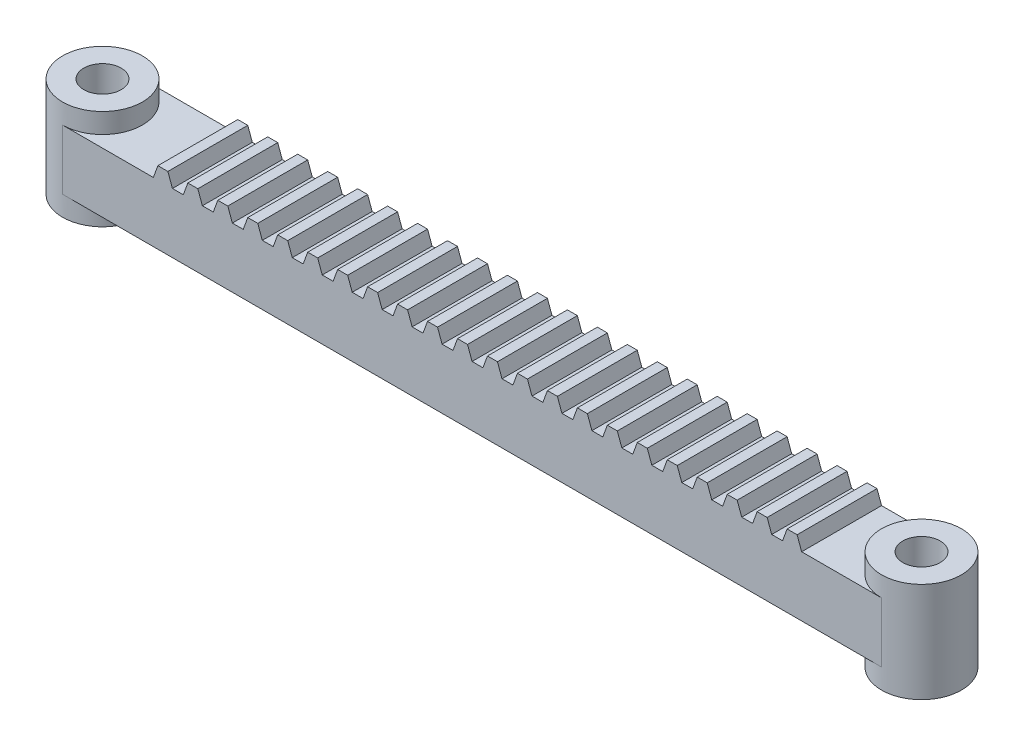
SolidWorks part; units mm, degrees
ref_plane "Front Plane" through (0, 0, 0) normal (0, 0, 1) x (1, 0, 0)
ref_plane "Top Plane" through (0, 0, 0) normal (0, 1, 0) x (1, 0, 0)
ref_plane "Right Plane" through (0, 0, 0) normal (1, 0, 0) x (0, 0, -1)
sketch "Sketch1" plane through (0, 0, 0) normal (0, 0, 1) x (1, 0, 0)
  line L0 (0, 12) -> (0, 0) construction
  line L1 (-82, 0) -> (82, 0)
  line L2 (82, 0) -> (82, 12)
  line L3 (82, 12) -> (66, 12)
  line L4 (-82, 0) -> (-82, 12)
  line L5 (-82, 12) -> (-63.8199, 12)
  line L7 (0, 12) -> (-0.9099, 14.5)
  line L8 (-0.9099, 14.5) -> (-2.9099, 14.5)
  line L9 (-2.9099, 14.5) -> (-3.8199, 12)
  line L10 (-3.8199, 12) -> (-6, 12)
  line L11 (-1.9099, 14.5019) -> (-1.9099, 13.6458) construction
  line L12 (6, 12) -> (5.0901, 14.5)
  line L13 (5.0901, 14.5) -> (3.0901, 14.5)
  line L14 (3.0901, 14.5) -> (2.1801, 12)
  line L15 (2.1801, 12) -> (0, 12)
  line L16 (-6.9099, 14.5) -> (-8.9099, 14.5)
  line L17 (4.0901, 14.5019) -> (4.0901, 13.6458) construction
  line L18 (12, 12) -> (11.0901, 14.5)
  line L19 (11.0901, 14.5) -> (9.0901, 14.5)
  line L20 (9.0901, 14.5) -> (8.1801, 12)
  line L21 (8.1801, 12) -> (6, 12)
  line L22 (-8.9099, 14.5) -> (-9.8199, 12)
  line L23 (10.0901, 14.5019) -> (10.0901, 13.6458) construction
  line L24 (18, 12) -> (17.0901, 14.5)
  line L25 (17.0901, 14.5) -> (15.0901, 14.5)
  line L26 (15.0901, 14.5) -> (14.1801, 12)
  line L27 (14.1801, 12) -> (12, 12)
  line L28 (-9.8199, 12) -> (-12, 12)
  line L29 (16.0901, 14.5019) -> (16.0901, 13.6458) construction
  line L30 (24, 12) -> (23.0901, 14.5)
  line L31 (23.0901, 14.5) -> (21.0901, 14.5)
  line L32 (21.0901, 14.5) -> (20.1801, 12)
  line L33 (20.1801, 12) -> (18, 12)
  line L34 (-7.9099, 14.5019) -> (-7.9099, 13.6458) construction
  line L35 (22.0901, 14.5019) -> (22.0901, 13.6458) construction
  line L36 (30, 12) -> (29.0901, 14.5)
  line L37 (29.0901, 14.5) -> (27.0901, 14.5)
  line L38 (27.0901, 14.5) -> (26.1801, 12)
  line L39 (26.1801, 12) -> (24, 12)
  line L40 (-6, 12) -> (-6.9099, 14.5)
  line L41 (28.0901, 14.5019) -> (28.0901, 13.6458) construction
  line L42 (36, 12) -> (35.0901, 14.5)
  line L43 (35.0901, 14.5) -> (33.0901, 14.5)
  line L44 (33.0901, 14.5) -> (32.1801, 12)
  line L45 (32.1801, 12) -> (30, 12)
  line L46 (-12.9099, 14.5) -> (-14.9099, 14.5)
  line L47 (34.0901, 14.5019) -> (34.0901, 13.6458) construction
  line L48 (42, 12) -> (41.0901, 14.5)
  line L49 (41.0901, 14.5) -> (39.0901, 14.5)
  line L50 (39.0901, 14.5) -> (38.1801, 12)
  line L51 (38.1801, 12) -> (36, 12)
  line L52 (-14.9099, 14.5) -> (-15.8199, 12)
  line L53 (40.0901, 14.5019) -> (40.0901, 13.6458) construction
  line L54 (48, 12) -> (47.0901, 14.5)
  line L55 (47.0901, 14.5) -> (45.0901, 14.5)
  line L56 (45.0901, 14.5) -> (44.1801, 12)
  line L57 (44.1801, 12) -> (42, 12)
  line L58 (-15.8199, 12) -> (-18, 12)
  line L59 (46.0901, 14.5019) -> (46.0901, 13.6458) construction
  line L60 (54, 12) -> (53.0901, 14.5)
  line L61 (53.0901, 14.5) -> (51.0901, 14.5)
  line L62 (51.0901, 14.5) -> (50.1801, 12)
  line L63 (50.1801, 12) -> (48, 12)
  line L64 (-13.9099, 14.5019) -> (-13.9099, 13.6458) construction
  line L65 (52.0901, 14.5019) -> (52.0901, 13.6458) construction
  line L66 (60, 12) -> (59.0901, 14.5)
  line L67 (59.0901, 14.5) -> (57.0901, 14.5)
  line L68 (57.0901, 14.5) -> (56.1801, 12)
  line L69 (56.1801, 12) -> (54, 12)
  line L70 (-12, 12) -> (-12.9099, 14.5)
  line L71 (58.0901, 14.5019) -> (58.0901, 13.6458) construction
  line L72 (66, 12) -> (65.0901, 14.5)
  line L73 (65.0901, 14.5) -> (63.0901, 14.5)
  line L74 (63.0901, 14.5) -> (62.1801, 12)
  line L75 (62.1801, 12) -> (60, 12)
  line L76 (-18.9099, 14.5) -> (-20.9099, 14.5)
  line L77 (64.0901, 14.5019) -> (64.0901, 13.6458) construction
  line L78 (-20.9099, 14.5) -> (-21.8199, 12)
  line L79 (-21.8199, 12) -> (-24, 12)
  line L80 (-19.9099, 14.5019) -> (-19.9099, 13.6458) construction
  line L81 (-18, 12) -> (-18.9099, 14.5)
  line L82 (-24.9099, 14.5) -> (-26.9099, 14.5)
  line L83 (-26.9099, 14.5) -> (-27.8199, 12)
  line L84 (-27.8199, 12) -> (-30, 12)
  line L85 (-25.9099, 14.5019) -> (-25.9099, 13.6458) construction
  line L86 (-24, 12) -> (-24.9099, 14.5)
  line L87 (-30.9099, 14.5) -> (-32.9099, 14.5)
  line L88 (-32.9099, 14.5) -> (-33.8199, 12)
  line L89 (-33.8199, 12) -> (-36, 12)
  line L90 (-31.9099, 14.5019) -> (-31.9099, 13.6458) construction
  line L91 (-30, 12) -> (-30.9099, 14.5)
  line L92 (-36.9099, 14.5) -> (-38.9099, 14.5)
  line L93 (-38.9099, 14.5) -> (-39.8199, 12)
  line L94 (-39.8199, 12) -> (-42, 12)
  line L95 (-37.9099, 14.5019) -> (-37.9099, 13.6458) construction
  line L96 (-36, 12) -> (-36.9099, 14.5)
  line L97 (-42.9099, 14.5) -> (-44.9099, 14.5)
  line L98 (-44.9099, 14.5) -> (-45.8199, 12)
  line L99 (-45.8199, 12) -> (-48, 12)
  line L100 (-43.9099, 14.5019) -> (-43.9099, 13.6458) construction
  line L101 (-42, 12) -> (-42.9099, 14.5)
  line L102 (-48.9099, 14.5) -> (-50.9099, 14.5)
  line L103 (-50.9099, 14.5) -> (-51.8199, 12)
  line L104 (-51.8199, 12) -> (-54, 12)
  line L105 (-49.9099, 14.5019) -> (-49.9099, 13.6458) construction
  line L106 (-48, 12) -> (-48.9099, 14.5)
  line L107 (-54.9099, 14.5) -> (-56.9099, 14.5)
  line L108 (-56.9099, 14.5) -> (-57.8199, 12)
  line L109 (-57.8199, 12) -> (-60, 12)
  line L110 (-55.9099, 14.5019) -> (-55.9099, 13.6458) construction
  line L111 (-54, 12) -> (-54.9099, 14.5)
  line L112 (-60.9099, 14.5) -> (-62.9099, 14.5)
  line L113 (-62.9099, 14.5) -> (-63.8199, 12)
  line L115 (-61.9099, 14.5019) -> (-61.9099, 13.6458) construction
  line L116 (-60, 12) -> (-60.9099, 14.5)
  line L117 (-63.8199, 12) -> (-66, 12) [skipped]
  point P2 (66.7393, 12)
  point P6 (0, 0)
  point P7 (-64.056, 12)
  dimension "D2" = 12
  dimension "D3" = 164
  dimension "D4" = 6
  dimension "D5" = 40
  dimension "D7" = 2.5
  dimension "D8" = 12
  dimension "D6" = 2
  dimension "D9" = 11
extrude "Boss-Extrude1" add sketch "Sketch1" along normal blind 8 and the other way blind 8 contours L109 L116 L112 L113 L5 L4 L1 L2 L3 L72 L73 L74 L75 L66 L67 L68 L69 L60 L61 L62 L63 L54 L55 L56 L57 L48 L49 L50 L51 L42 L43 L44 L45 L36 L37 L38 L39 L30 L31 L32 L33 L24 L25 L26 L27 L18 L19 L20 L21 L12 L13 region at (0.082, 6.5355, 0)
sketch "Sketch2" plane through (0, 12, 0) normal (0, 1, 0) x (1, 0, 0)
  line L0 (0, 25.9758) -> (0, -24.152) construction
  line L1 (82, 8) -> (82, -8) construction
  circle A0 centre (82, 0) radius 8
  circle A1 centre (82, 0) radius 3.75
  circle A2 centre (-82, 0) radius 3.75
  circle A3 centre (-82, 0) radius 8
  line M5 (82, -8) -> (82, 8)
  dimension "D1" = 16
  dimension "D2" = 7.5
  dimension "D3" = 0
extrude "Boss-Extrude2" add sketch "Sketch2" along normal blind 4 and the other way blind 16
extrude "Cut-Extrude1" cut sketch "Sketch2<2>" against normal blind 16 contours A2 | A1 M5 | A1 M5 region at (80.4085, 12, 0) region at (83.5915, 12, 0) region at (-82, 12, 0)
sketch "Sketch2<2>" plane through (0, 12, 0) normal (0, 1, 0) x (1, 0, 0) same geometry as "Sketch2"
